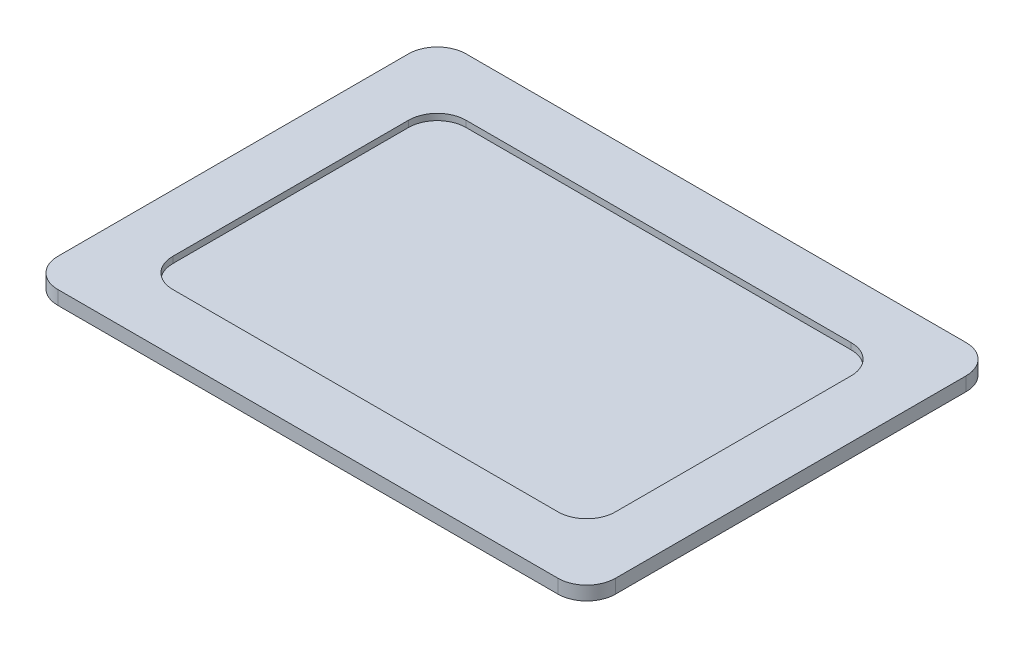
SolidWorks part; units mm, degrees
material "ABS"
ref_plane "Front Plane" through (0, 0, 0) normal (0, 0, 1) x (1, 0, 0)
ref_plane "Top Plane" through (0, 0, 0) normal (0, 1, 0) x (1, 0, 0)
ref_plane "Right Plane" through (0, 0, 0) normal (1, 0, 0) x (0, 0, -1)
sketch "Sketch1" plane through (0, 0, 0) normal (0, 1, 0) x (1, 0, 0)
  line L1 (-48.5, -35.5) -> (48.5, -35.5)
  line L2 (-48.5, -35.5) -> (-48.5, 35.5)
  line L3 (-48.5, 35.5) -> (48.5, 35.5)
  line L4 (48.5, -35.5) -> (48.5, 35.5)
  line L5 (-48.5, -35.5) -> (48.5, 35.5) construction
  line L6 (-48.5, 35.5) -> (48.5, -35.5) construction
  point P0 (0, 0)
  dimension "D1" = 71
  dimension "D2" = 97
extrude "Boss-Extrude1" add sketch "Sketch1" along normal blind 1.2 and the other way blind 1.2
sketch "Sketch2" plane through (0, 1.2, 0) normal (0, 1, 0) x (1, 0, 0)
  line L0 (-48.5, 35.5) -> (48.5, -35.5) construction
  line L2 (-38.5, -25.5) -> (38.5, -25.5)
  line L3 (-38.5, -25.5) -> (-38.5, 25.5)
  line L4 (-38.5, 25.5) -> (38.5, 25.5)
  line L5 (38.5, -25.5) -> (38.5, 25.5)
  line L6 (-38.5, -25.5) -> (38.5, 25.5) construction
  line L7 (-38.5, 25.5) -> (38.5, -25.5) construction
  point P4 (0, 0)
  dimension "D1" = 77
  dimension "D2" = 51
extrude "Cut-Extrude1" cut sketch "Sketch2" against normal offset from surface (1.1 mm away) 0.1 contours L3 L4 L5 L2 up to plane "Top Plane"
fillet "Fillet1" radius 5 4 edges at (38.5, 0.65, -25.5) (-38.5, 0.65, 25.5) (38.5, 0.65, 25.5) (-38.5, 0.65, -25.5)
mirror "Mirror3" about plane through (0, 0, 0) normal (0, 1, 0) of "Fillet1", "Cut-Extrude1"
fillet "Fillet2" radius 5 4 edges at (48.5, 0, -35.5) (-48.5, 0, 35.5) (48.5, 0, 35.5) (-48.5, 0, -35.5)
